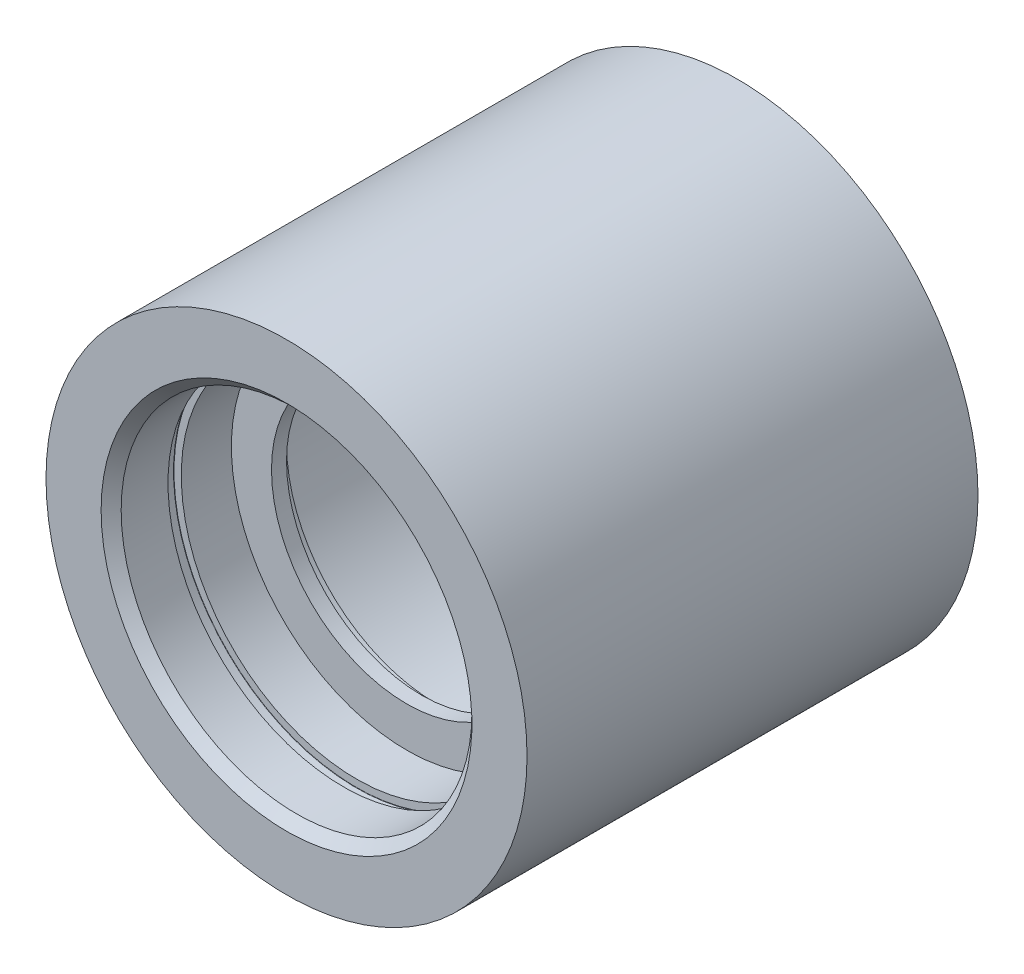
SolidWorks part; units mm, degrees
material "AISI 304"
ref_plane "Спереди" through (0, 0, 0) normal (0, 0, 1) x (1, 0, 0)
ref_plane "Сверху" through (0, 0, 0) normal (0, 1, 0) x (1, 0, 0)
ref_plane "Справа" through (0, 0, 0) normal (1, 0, 0) x (0, 0, -1)
sketch "Эскиз1" plane through (0, 0, 0) normal (1, 0, 0) x (0, 0, -1)
  line L0 (0, 0) -> (0, 48) construction
  line L1 (0, 48) -> (90, 48)
  line L2 (90, 48) -> (90, 40)
  line L3 (90, 40) -> (30, 40)
  line L6 (24, 27) -> (24, 35)
  line L7 (24, 35) -> (0, 35)
  line L8 (0, 35) -> (0, 48)
  line L9 (0, 0) -> (110.0063, 0) construction
  line L10 (24, 27) -> (27, 27)
  line L11 (27, 27) -> (27, 30)
  line L12 (27, 30) -> (30, 30)
  line L13 (30, 30) -> (30, 40)
  dimension "D1" = 48
  dimension "D2" = 35
  dimension "D3" = 27
  dimension "D4" = 40
  dimension "D5" = 24
  dimension "D6" = 6
  dimension "D7" = 8
  dimension "63" = 60
  dimension "D8" = 30
  dimension "D9" = 3
  dimension "D10" = 3
revolve "Повернуть1" add sketch "Эскиз1" angle 360 about L9
ref_plane "Плоскость1" through (0, 0, -14) normal (0, 0, 1) x (1, 0, 0)
sketch "Эскиз2" plane through (0, 0, -14) normal (0, 0, 1) x (1, 0, 0)
  circle A0 centre (0, 0) radius 36.5
  dimension "D1" = 73
extrude "Вырез-Вытянуть1" cut sketch "Эскиз2" along normal blind 2.65
ref_plane "Плоскость2" through (0, 0, -69) normal (0, 0, -1) x (-1, 0, 0)
sketch "Эскиз3" plane through (0, 0, -69) normal (0, 0, -1) x (-1, 0, 0)
  circle A0 centre (0, 0) radius 41.75
  dimension "D1" = 83.5
extrude "Вырез-Вытянуть2" cut sketch "Эскиз3" along normal blind 2.65
fillet "Скругление1" radius 0.05 4 edges at (-41.75, 0, -71.65) (-41.75, 0, -69) (36.5, 0, -11.35) (36.5, 0, -14)
chamfer "Фаска2" distance 2 angle 45 2 edges at (35, 0, 0) (40, 0, -90)
ref_axis "Ось1" through (0, 0, -80.9) along (0, 0, 1)
ref_plane "Плоскость3" through (0, 0, 0) normal (0.9239, 0.3827, 0) x (0, 0, 1)
